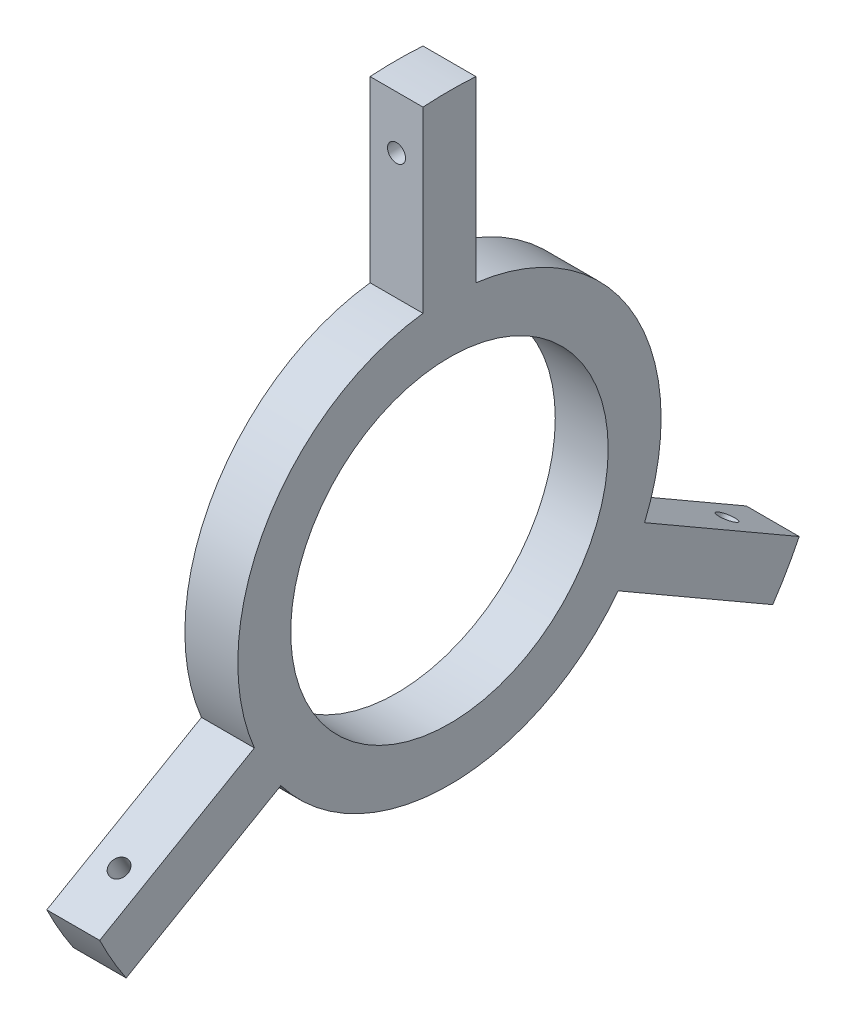
SolidWorks part; units mm, degrees
ref_plane "Plan de face" through (0, 0, 0) normal (0, 0, 1) x (1, 0, 0)
ref_plane "Plan de dessus" through (0, 0, 0) normal (0, 1, 0) x (1, 0, 0)
ref_plane "Plan de droite" through (0, 0, 0) normal (1, 0, 0) x (0, 0, -1)
sketch "Esquisse2" plane through (0, 0, 0) normal (0, 0, 1) x (1, 0, 0)
  line L0 (-5, 0) -> (5, 0)
  line L1 (5, 0) -> (5, 73.61)
  line L2 (5, 73.61) -> (-5, 73.61)
  line L3 (-5, 73.61) -> (-5, 0)
  dimension "D1" = 73.61
  dimension "D2" = 10
extrude "Boss.-Extru.1" add sketch "Esquisse2" along normal blind 5 and the other way blind 5
sketch "Esquisse3" plane through (5, 0, 0) normal (1, 0, 0) x (0, 0, -1)
  line L0 (0, 0) -> (0, 73.61) construction
  line L1 (-25.3992, 69.0892) -> (-25.3992, 83.5877)
  line L2 (-25.3992, 83.5877) -> (25.3992, 83.5877)
  line L3 (25.3992, 83.5877) -> (25.3992, 69.0892)
  line L4 (5, 75) -> (-5, 75) construction
  line L5 (-5, 0) -> (-5, 73.61) construction
  arc A0 (-25.3992, 69.0892) -> (25.3992, 69.0892) centre (0, 0) cw
  dimension "D1" = 73.61
  dimension "D2" = 30.3992
  dimension "D3" = 8.5877
extrude "Enlèv. mat.-Extru.1" cut sketch "Esquisse3" against normal through all
sketch "Esquisse5" plane through (0, 0, 0) normal (0, 1, 0) x (1, 0, 0)
  line L0 (0, 0) -> (7.3012, 0) construction
ref_plane "Plan3" through (0, 0, 0) normal (0, 0, -1) x (-1, 0, 0)
ref_plane "Plan4" through (0, 73.44, 0) normal (0, -1, 0) x (-1, 0, 0)
hole_wizard "Dégagement M31" positions "Esquisse6" profile "Esquisse7" hole size "M3" standard "ISO" end condition through all
sketch "Esquisse6" plane through (0, 0, -5) normal (0, 0, -1) x (-1, 0, 0)
  line L0 (-5.5, 73.44) -> (5.5, 73.44) construction
  line L1 (0, 63.44) -> (5, 73.44) construction
  line L3 (0, 63.44) -> (-5, 73.44) construction
  point P35 (0, 63.44)
  dimension "D1" = 10
sketch "Esquisse7" plane through (0, 63.44, -5) normal (1, 0, 0) x (0, 1, 0)
  line L0 (0, 0) -> (0, 73.6009)
  line L1 (0, 73.6009) -> (1.7, 73.6009)
  line L2 (1.7, 73.6009) -> (1.7, 0)
  line L5 (1.7, 0) -> (0, 0)
  line L11 (0, -6.35) -> (0, 107.95) construction
  dimension "Diamètre du perçage jusqu'au prochain" = 3.4
  dimension "Profondeur du perçage jusqu'au prochain" = 73.6009
pattern_circular "Répétition circulaire1" count 3 over 360 about axis through (0, 0, 0) along (1, 0, 0) of "Boss.-Extru.1", "Enlèv. mat.-Extru.1", "Dégagement M31" reverse direction yes
ref_plane "Plan1" [suppressed] through (0, 0, 0) normal (0, 0.866, 0.5) x (1, 0, 0)
ref_plane "Plan2" [suppressed] through (0, 0, 0) normal (0, 0.866, -0.5) x (1, 0, 0)
ref_plane "Plan5" [suppressed] through (0, -36.72, 63.6009) normal (0, 0.5, -0.866) x (-1, 0, 0)
ref_plane "Plan6" [suppressed] through (0, -36.72, -63.6009) normal (0, -0.5, -0.866) x (-1, 0, 0)
ref_plane "Plan7" through (0, 0, 0) normal (1, 0, 0) x (0, 0, -1)
sketch "Esquisse8" plane through (5, 0, 0) normal (1, 0, 0) x (0, 0, -1)
  circle A0 centre (0, 0) radius 40
  dimension "D1" = 80
extrude "Boss.-Extru.2" add sketch "Esquisse8" against normal up to surface (10 mm away) up to face at (-5, 0, 0)
sketch "Esquisse9" plane through (5, 0, 0) normal (1, 0, 0) x (0, 0, -1)
  circle A0 centre (0, 0) radius 30
  arc A1 (36.8693, -15.513) -> (5, 39.6863) centre (0, 0) ccw construction
  dimension "D1" = 10
extrude "Enlèv. mat.-Extru.3" cut sketch "Esquisse9" against normal through all
ref_plane "Plan8" through (0, 0, 0) normal (0, 0.866, -0.5) x (1, 0, 0)
ref_plane "Plan9" through (0, 0, 0) normal (0, 0.866, 0.5) x (1, 0, 0)
